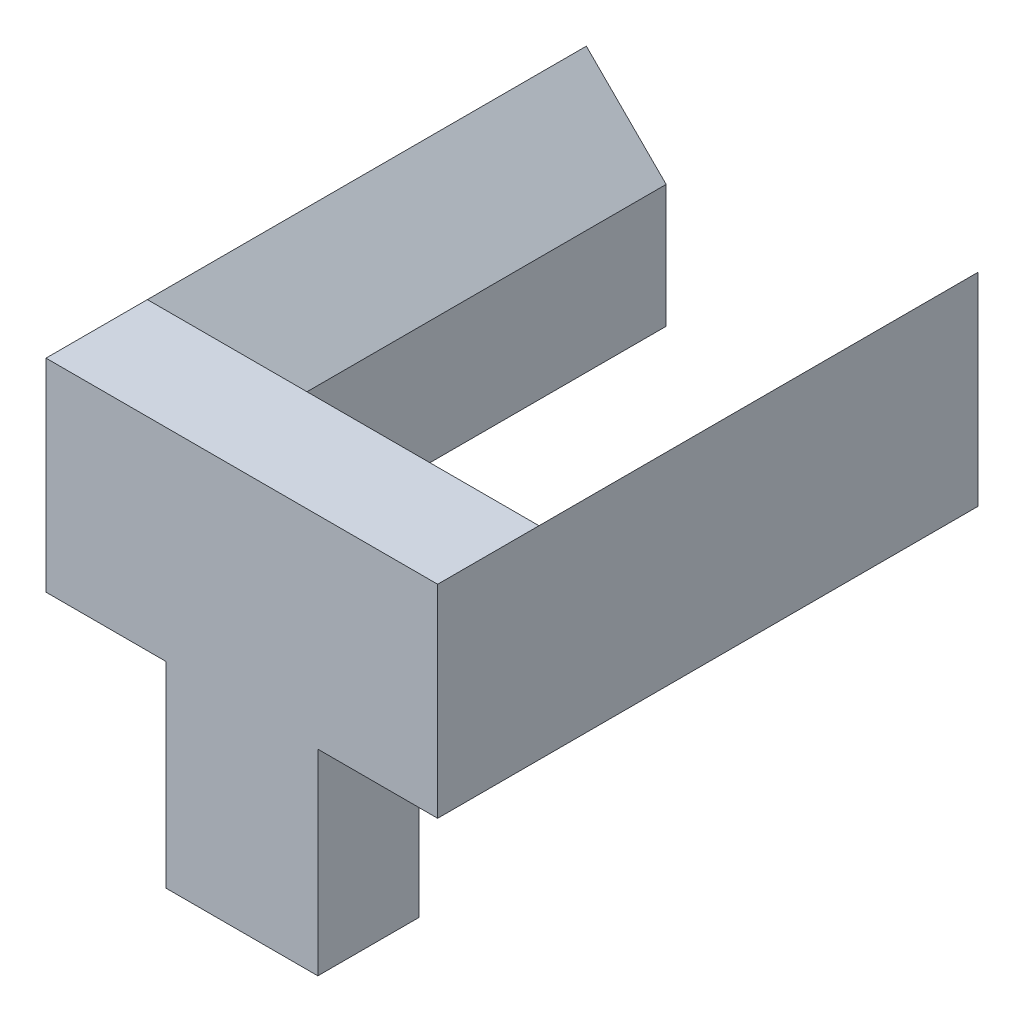
SolidWorks part; units mm, degrees
ref_plane "Front Plane" through (0, 0, 0) normal (0, 0, 1) x (1, 0, 0)
ref_plane "Top Plane" through (0, 0, 0) normal (0, 1, 0) x (1, 0, 0)
ref_plane "Right Plane" through (0, 0, 0) normal (1, 0, 0) x (0, 0, -1)
sketch "Sketch1" plane through (0, 0, 0) normal (0, 1, 0) x (1, 0, 0)
  line L0 (-13.9881, 12.8425) -> (-13.9881, -12.5575)
  line L1 (-13.9881, -12.5575) -> (24.1119, -12.5575)
  line L2 (24.1119, -12.5575) -> (24.1119, 12.8425)
  line L3 (24.1119, 12.8425) -> (-13.9881, 12.8425)
  line L4 (5.0619, 12.8425) -> (5.0619, -12.5575) construction
extrude "Boss-Extrude1" add sketch "Sketch1" along normal blind 99.9998 contours L3 L0 L1 L2
sketch "Sketch2" plane through (24.1119, 0, 0) normal (1, 0, 0) x (0, 0, -1)
  line L0 (-12.5575, 99.9998) -> (12.8425, 99.9998)
  line L1 (12.8425, 99.9998) -> (12.8425, 49.1998)
  line L2 (12.8425, 99.9998) -> (12.8425, 0) construction
  line L3 (12.8425, 49.1998) -> (-12.5575, 49.1998)
  line L4 (-12.5575, 99.9998) -> (-12.5575, 0) construction
  line L5 (-12.5575, 49.1998) -> (-12.5575, 99.9998)
extrude "Boss-Extrude2" add sketch "Sketch2" along normal blind 30.0228 contours L1 L3 L5 L0
sketch "Sketch3" plane through (-13.9881, 0, 0) normal (-1, 0, 0) x (0, 0, 1)
  line L0 (12.5575, 99.9998) -> (12.5575, 0) construction
  line L1 (-12.8425, 99.9998) -> (12.5575, 99.9998)
  line L2 (-12.8425, 99.9998) -> (-12.8425, 49.1998)
  line L3 (-12.8425, 49.1998) -> (12.5575, 49.1998)
  line L4 (12.5575, 99.9998) -> (12.5575, 49.1998)
extrude "Boss-Extrude3" add sketch "Sketch3" along normal blind 30.0228
sketch "Sketch4" plane through (0, 0, -12.8425) normal (0, 0, -1) x (-1, 0, 0)
  line L0 (-54.1347, 99.9998) -> (-54.1347, 49.1998)
  line L4 (-36.1667, 79.9998) -> (-54.1347, 99.9998)
  line L5 (-36.1667, 79.9998) -> (-36.1667, 49.1998)
  line L6 (-54.1347, 49.1998) -> (-24.1119, 49.1998) construction
  line L7 (-36.1667, 49.1998) -> (-54.1347, 49.1998)
extrude "Boss-Extrude4" add sketch "Sketch4" along normal blind 110.0074
sketch "Sketch5" plane through (0, 0, -12.8425) normal (0, 0, -1) x (-1, 0, 0)
  line L0 (44.0109, 99.9998) -> (44.0109, 49.1998)
  line L1 (44.0109, 49.1998) -> (24.0109, 49.1998)
  line L2 (44.0109, 49.1998) -> (13.9881, 49.1998) construction
  line L3 (24.0109, 49.1998) -> (24.0109, 79.9998)
  line L4 (24.0109, 79.9998) -> (44.0109, 99.9998)
extrude "Boss-Extrude5" add sketch "Sketch5" along normal blind 110.0074 contours L4 L0 L1 L3
sketch "Sketch8" plane through (0, 0, 0) normal (0, -1, 0) x (1, 0, 0)
  line L0 (5.0619, 12.5575) -> (5.0619, -12.8425) construction
  line L1 (-13.9881, 12.5575) -> (24.1119, 12.5575) construction
  line L2 (24.1119, -12.8425) -> (-13.9881, -12.8425) construction
  line L3 (5.0619, -0.1425) -> (17.5079, -0.1425) construction
  line L4 (5.0619, -0.1425) -> (-5.3521, -0.1425) construction
  circle A0 centre (-5.3521, -0.1425) radius 3.175
  circle A1 centre (17.5079, -0.1425) radius 3.175
  dimension "D1" = 6.35
  dimension "D2" = 6.35
extrude "Cut-Extrude1" cut sketch "Sketch8" against normal blind 12.7
